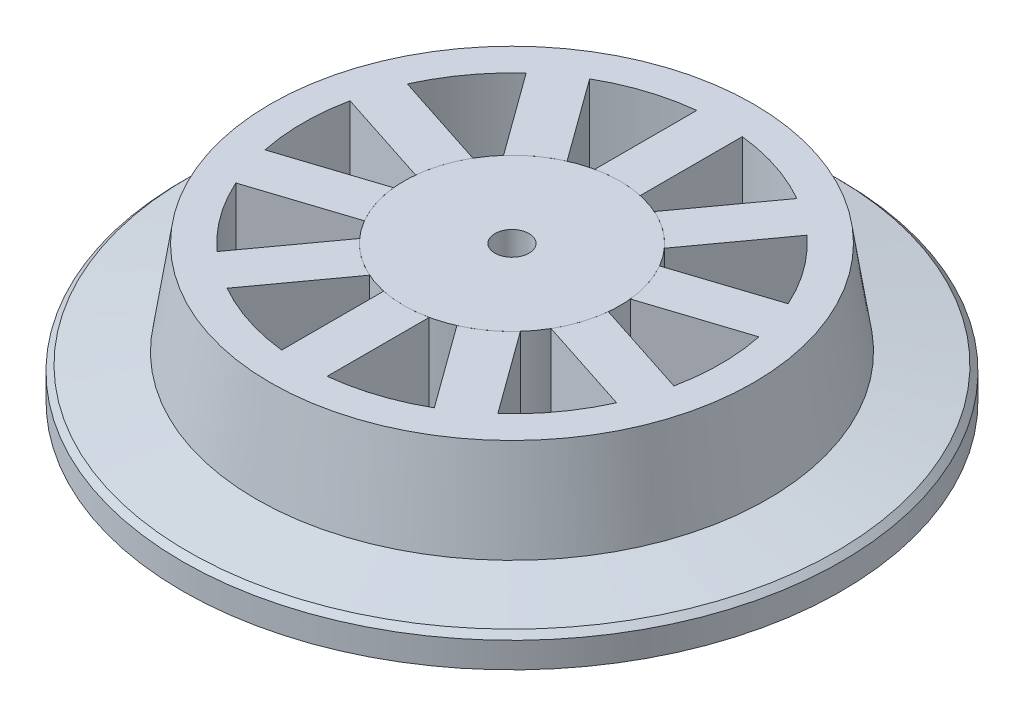
SolidWorks part; units mm, degrees
other "标注1"
sketch "草图3" plane through (-22.25, 4, -10) normal (-0.231, 0.6469, -0.7268) x (-0.9696, -0.2151, 0.1167)
ref_plane "前视基准面" through (0, 0, 0) normal (0, 0, 1) x (1, 0, 0)
ref_plane "上视基准面" through (0, 0, 0) normal (0, 1, 0) x (1, 0, 0)
ref_plane "右视基准面" through (0, 0, 0) normal (1, 0, 0) x (0, 0, -1)
other "Configuration Table"
sketch "草图4" plane through (0, 0, 0) normal (0, 1, 0) x (1, 0, 0)
  circle A0 centre (0, 0) radius 11.6
  circle A1 centre (0, 0) radius 0.6
  circle A2 centre (0, 0) radius 9
  dimension "D1" = 23.2
  dimension "D2" = 1.2
  dimension "D3" = 18
extrude "凸台-拉伸1" add sketch "草图4" along normal blind 1.1 contours A0 | A1
extrude "凸台-拉伸2" add sketch "草图4<3>" along normal blind 3.3 from offset 1.5 contours A2 | A1
sketch "草图4<3>" plane through (0, 0, 0) normal (0, 1, 0) x (1, 0, 0) same geometry as "草图4"
chamfer "倒角1" distance 0.2 angle 45 1 edges at (0, 1.1, 11.6)
loft "放样1" add section edge at (0, 1.5, 9) section edge at (0, 1.1, 11.4)
extrude "切除-拉伸2" cut sketch "草图4<4>" along normal through all contours A1
sketch "草图4<4>" plane through (0, 0, 0) normal (0, 1, 0) x (1, 0, 0) same geometry as "草图4"
chamfer "倒角2" distance 3.3 distance2 0.5 1 edges at (0, 4.8, 9) first distance on face at (0, 4.8, 9)
sketch "草图5" plane through (0, 4.8, 0) normal (0, 1, 0) x (1, 0, 0)
  line L0 (-0.8, 3.7148) -> (-0.8, 7.3063)
  line L1 (0, 3.8) -> (0, 7.35) construction
  line L2 (0.8, 7.3063) -> (0.8, 3.7148)
  circle A0 centre (0, 0) radius 3.8
  circle A1 centre (0, 0) radius 7.35
  dimension "D1" = 7.6
  dimension "D2" = 14.7
  dimension "D3" = 0.8
  dimension "D4" = 0.8
extrude "切除-拉伸4" cut sketch "草图5" against normal through all contours L0 A1 L2 A0 | A0 L1 A1 L0 | L1 A0 L2 A1 region at (-2.5179, 4.8, 3.1178) region at (-0.4008, 4.8, -5.5535) region at (0.4008, 4.8, -5.5535)
extrude "凸台-拉伸3" add sketch "草图5<4>" against normal up to surface (4.8 mm away) contours L1 A0 L2 A1 | A0 L1 A1 L0 region at (-0.4008, 4.8, -5.5535) region at (0.4008, 4.8, -5.5535) up to face at (0, 0, 7.35)
sketch "草图5<4>" plane through (0, 4.8, 0) normal (0, 1, 0) x (1, 0, 0) same geometry as "草图5"
pattern_circular "阵列(圆周)2" count 10 over 360 about axis through (0, 1.1, 0) along (0, -1, 0) of "凸台-拉伸3" reverse direction yes
